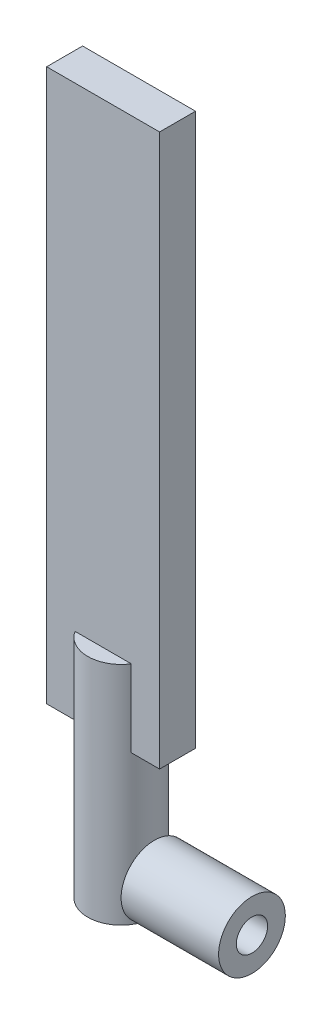
SolidWorks part; units mm, degrees
ref_plane "Спереди" through (0, 0, 0) normal (0, 0, 1) x (1, 0, 0)
ref_plane "Сверху" through (0, 0, 0) normal (0, 1, 0) x (1, 0, 0)
ref_plane "Справа" through (0, 0, 0) normal (1, 0, 0) x (0, 0, -1)
sketch "Эскиз1" plane through (0, 0, 0) normal (1, 0, 0) x (0, 0, -1)
  circle A0 centre (0, 0) radius 6.5
  dimension "D1" = 13
extrude "Бобышка-Вытянуть1" add sketch "Эскиз1" along normal blind 19
sketch "Эскиз2" plane through (19, 0, 0) normal (1, 0, 0) x (0, 0, -1)
  circle A0 centre (0, 0) radius 3.05
  dimension "D1" = 6.1
extrude "Вырез-Вытянуть1" cut sketch "Эскиз2" against normal blind 5
sketch "Эскиз3" plane through (0, 0, 0) normal (0, 1, 0) x (1, 0, 0)
  line L0 (0, 0) -> (-6.5, 0) construction
  line L1 (0, 6.5) -> (0, -6.5) construction
  circle A0 centre (-6.5, 0) radius 6.5
  dimension "D1" = 13
extrude "Бобышка-Вытянуть2" add sketch "Эскиз3" along normal blind 37.5 and the other way blind 6.5 separate body
sketch "Эскиз4" plane through (0, 37.5, 0) normal (0, 1, 0) x (1, 0, 0)
  line L0 (-17.5, -3.5) -> (4.5, 3.5) construction
  line L1 (-17.5, 3.5) -> (4.5, 3.5)
  line L2 (-17.5, 3.5) -> (-17.5, -3.5)
  line L3 (-17.5, -3.5) -> (4.5, -3.5)
  line L4 (4.5, 3.5) -> (4.5, -3.5)
  circle A0 centre (-6.5, 0) radius 6.5 construction
  point P7 (-6.5, 0)
  dimension "D1" = 22
  dimension "D2" = 7
extrude "Бобышка-Вытянуть3" add sketch "Эскиз4" along normal blind 92.5 and the other way blind 15
